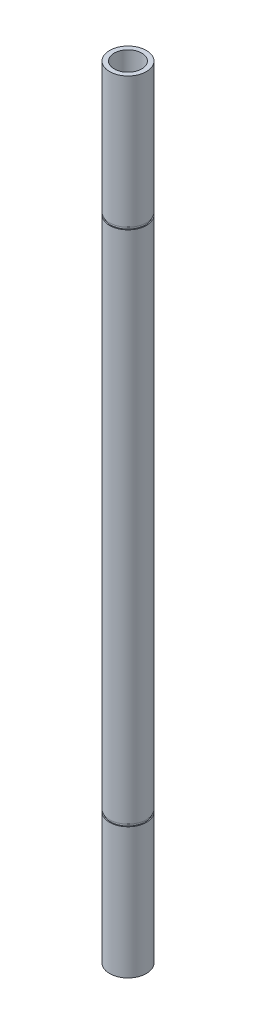
SolidWorks part; units mm, degrees
material "1060 Alloy"
ref_plane "Front Plane" through (0, 0, 0) normal (0, 0, 1) x (1, 0, 0)
ref_plane "Top Plane" through (0, 0, 0) normal (0, 1, 0) x (1, 0, 0)
ref_plane "Right Plane" through (0, 0, 0) normal (1, 0, 0) x (0, 0, -1)
sketch "Sketch1" plane through (0, 0, 0) normal (0, 0, 1) x (1, 0, 0)
  line L0 (0, 64.3023) -> (0, -80.2699) construction
  line L1 (-3, 85) -> (-4, 85)
  line L2 (-4, 85) -> (-4, 56.5)
  line L3 (-4, 56.5) -> (-3.8, 56.5)
  line L4 (-3.8, 56.5) -> (-3.8, 56)
  line L5 (-3.8, 56) -> (-4, 56)
  line L6 (-30.6471, 0) -> (35.9901, 0) construction
  line L7 (-4, 56) -> (-4, -56)
  line L8 (-3.8, -56) -> (-4, -56)
  line L9 (-3.8, -56.5) -> (-3.8, -56)
  line L10 (-4, -56.5) -> (-3.8, -56.5)
  line L11 (-4, -85) -> (-4, -56.5)
  line L12 (-3, -85) -> (-4, -85)
  line L13 (-3, 85) -> (-3, -85)
  point P11 (-4, 70.75)
  point P14 (-4, 0)
  dimension "D1" = 170
  dimension "D2" = 8
  dimension "D3" = 0.5
  dimension "D4" = 0.2
  dimension "D5" = 28.5
  dimension "D6" = 1
revolve "Revolve2" add sketch "Sketch1" angle 360 about L0
